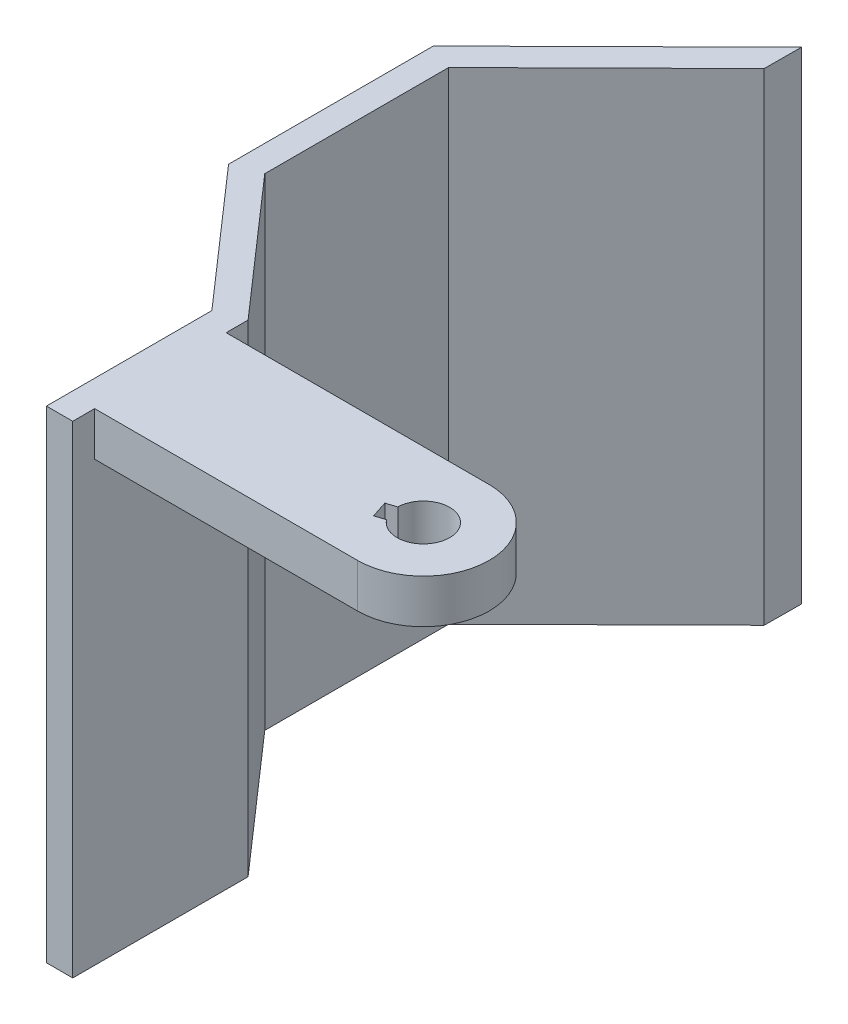
SolidWorks part; units mm, degrees
ref_plane "Front Plane" through (0, 0, 0) normal (0, 0, 1) x (1, 0, 0)
ref_plane "Top Plane" through (0, 0, 0) normal (0, 1, 0) x (1, 0, 0)
ref_plane "Right Plane" through (0, 0, 0) normal (1, 0, 0) x (0, 0, -1)
sketch "Sketch1" plane through (0, 0, 0) normal (0, 1, 0) x (1, 0, 0)
  line L0 (0, 0) -> (0, 18.8714)
  line L1 (0, 18.8714) -> (-13.5055, 34.2807)
  line L2 (-13.5055, 34.2807) -> (-13.5055, 57.6371)
  line L3 (-13.5055, 57.6371) -> (7.6165, 78.5217)
  line L9 (3, 0) -> (0, 0)
  line L10 (9.3102, 0) -> (0, 0) construction
  line L12 (3, 20) -> (-10.5055, 35.4093)
  line L13 (-10.5055, 35.4093) -> (-10.5055, 56.3845)
  line L14 (-10.5055, 56.3845) -> (7.5925, 74.2792)
  line L15 (7.5925, 74.2792) -> (7.6165, 78.5217)
  line L16 (9.3102, 3) -> (3, 3) construction
  line L18 (7.5925, 74.2792) -> (12.0785, 69.7422) construction
  line L19 (7.6165, 78.5217) -> (14.2117, 71.8516) construction
  line L20 (3, 0) -> (3, 20)
  line L21 (3, 3) -> (3, 20) construction
  line L22 (3, 2.5) -> (33, 2.5)
  line L23 (3, 17.5) -> (33, 17.5)
  arc A0 (33, 2.5) -> (33, 17.5) centre (33, 10) ccw
  point P22 (3, 10)
  dimension "D2" = 15
  dimension "D1" = 3
  dimension "D3" = 30
  dimension "D4" = 20
extrude "Boss-Extrude1" add sketch "Sketch1" along normal blind 55 contours L9 L20 L12 L13 L14 L15 L3 L2 L1 L0 region at (0.8131, 0, -9.4357)
extrude "Boss-Extrude2" add sketch "Sketch1<3>" against normal blind 5 from surface contours L22 A0 L23 L20 region at (20.9843, 0, -10) starting at face at (-2.6813, 55, -37.5384)
sketch "Sketch1<3>" plane through (0, 0, 0) normal (0, 1, 0) x (1, 0, 0) same geometry as "Sketch1"
ref_axis "GearAxis" through (33, 50, -10) along (0, 1, 0)
hole_wizard "M3 Clearance Hole1" positions "Sketch2" profile "Sketch3" hole size "M3" standard "ANSI Metric" end condition through all
sketch "Sketch2" plane through (0, 55, 0) normal (0, 1, 0) x (1, 0, 0)
  point P0 (33, 10)
sketch "Sketch3" plane through (33, 55, -10) normal (1, 0, 0) x (0, 0, 1)
  line L0 (0, 0) -> (0, 55)
  line L1 (0, 55) -> (1.7, 55)
  line L2 (1.7, 55) -> (1.7, 0.025)
  line L3 (1.7, 0.025) -> (1.725, 0)
  line L5 (1.725, 0) -> (0, 0)
  line L6 (-1.7, 0.025) -> (-1.725, 0) construction
  line L11 (0, -6.35) -> (0, 107.95) construction
  dimension "Thru Hole Dia." = 3.4
  dimension "Thru Hole Depth" = 55
  dimension "Near C'Sink Dia." = 3.45
  dimension "Near C'Sink Angle" = 90
sketch "Sketch4" plane through (0, 55, 0) normal (0, 1, 0) x (1, 0, 0)
  line L0 (30.001, 10.077) -> (28.8868, 9.715) construction
  line L1 (28.8868, 9.715) -> (29.5048, 7.8129) construction
  line L2 (29.5048, 7.8129) -> (30.619, 8.1749) construction
  line L3 (30.001, 10.077) -> (28.8868, 9.715)
  line L4 (28.8868, 9.715) -> (29.5048, 7.8129)
  line L5 (29.5048, 7.8129) -> (30.619, 8.1749)
  arc A0 (30.619, 8.1749) -> (30.001, 10.077) centre (33, 10) ccw construction
  arc A1 (30.619, 8.1749) -> (30.001, 10.077) centre (33, 10) ccw
extrude "Cut-Extrude1" cut sketch "Sketch4" against normal through all
